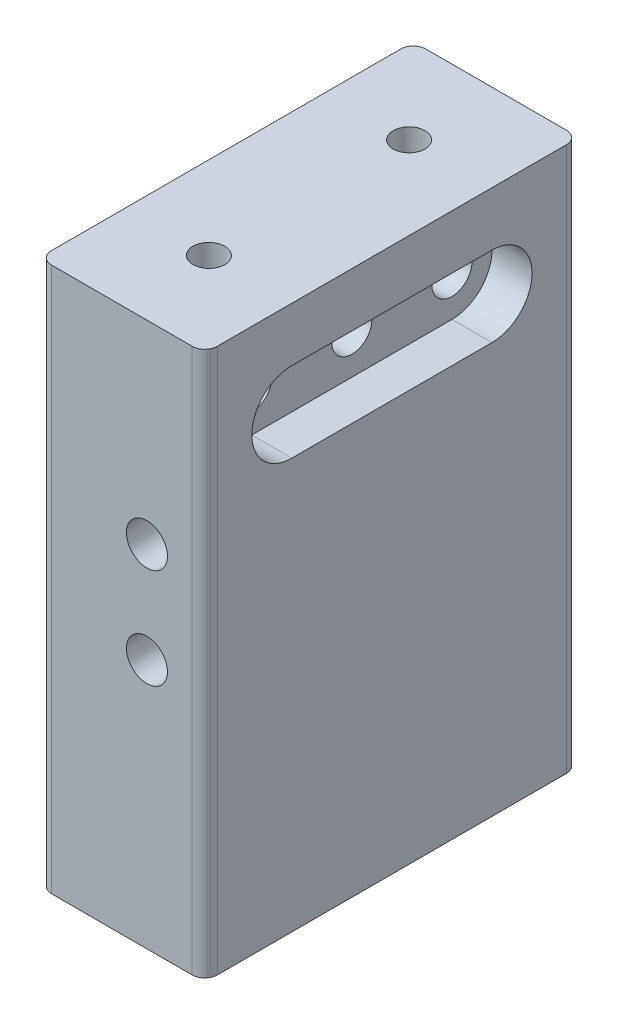
SolidWorks part; units mm, degrees
material "6061-T6 (SS)"
ref_plane "Front Plane" through (0, 0, 0) normal (0, 0, 1) x (1, 0, 0)
ref_plane "Top Plane" through (0, 0, 0) normal (0, 1, 0) x (1, 0, 0)
ref_plane "Right Plane" through (0, 0, 0) normal (1, 0, 0) x (0, 0, -1)
sketch "Sketch1" plane through (0, 0, 0) normal (0, 1, 0) x (1, 0, 0)
  line L1 (-10.5156, -23.7427) -> (10.5156, -23.7427)
  line L2 (-10.5156, -23.7427) -> (-10.5156, 23.7426)
  line L3 (-10.5156, 23.7426) -> (10.5156, 23.7426)
  line L4 (10.5156, -23.7427) -> (10.5156, 23.7426)
  line L5 (-10.5156, -23.7427) -> (10.5156, 23.7426) construction
  line L6 (-10.5156, 23.7426) -> (10.5156, -23.7427) construction
  point P0 (0, 0)
  dimension "D1" = 21.0312
  dimension "D2" = 47.4853
extrude "Boss-Extrude1" add sketch "Sketch1" along normal mid plane 63.5
sketch "Sketch2" plane through (0, 0, 23.7427) normal (0, 0, 1) x (1, 0, 0)
  line L5 (-10.5156, 31.75) -> (10.5156, 31.75) construction
  circle A1 centre (3.175, 0) radius 2.6035
  circle A2 centre (3.175, 12.7) radius 2.6035
  dimension "D3" = 19.05
  dimension "D1" = 7.3406
  dimension "D2" = 5.207
  dimension "D4" = 12.7
extrude "Cut-Extrude1" cut sketch "Sketch2" against normal through all
sketch "Sketch4" plane through (10.5156, 0, 0) normal (1, 0, 0) x (0, 0, -1)
  line L0 (-23.7427, 31.75) -> (23.7426, 31.75) construction
  circle A0 centre (-12.7, 25.4) radius 2.5527
  circle A1 centre (12.7, 25.4) radius 2.5527
  circle A2 centre (0, 25.4) radius 2.5527
  dimension "D5" = 5.1054
  dimension "D1" = 6.35
  dimension "D3" = 12.7
  dimension "D4" = 12.7
extrude "Cut-Extrude3" cut sketch "Sketch4" against normal through all
fillet "Fillet1" radius 1.5875 4 edges at (10.5156, 0, 23.7427) (-10.5156, 0, 23.7427) (-10.5156, 0, -23.7426) (10.5156, 0, -23.7426)
sketch "Sketch7" plane through (10.5156, 0, 0) normal (1, 0, 0) x (0, 0, -1)
  line L0 (-12.7, 25.4) -> (12.7, 25.4) construction
  line L1 (-12.7, 30.48) -> (12.7, 30.48)
  line L2 (-12.7, 20.32) -> (12.7, 20.32)
  arc A0 (-12.7, 30.48) -> (-12.7, 20.32) centre (-12.7, 25.4) ccw
  arc A1 (12.7, 20.32) -> (12.7, 30.48) centre (12.7, 25.4) ccw
  point P4 (0, 25.4)
  dimension "D1" = 5.08
extrude "Cut-Extrude5" cut sketch "Sketch7" against normal blind 5.08
sketch "Sketch8" plane through (0, 31.75, 0) normal (0, 1, 0) x (1, 0, 0)
  line L4 (-8.9281, -23.7427) -> (8.9281, -23.7427)
  line L5 (10.5156, -22.1552) -> (10.5156, 22.1551)
  line L6 (8.9281, 23.7426) -> (-8.9281, 23.7426)
  line L7 (-10.5156, 22.1551) -> (-10.5156, -22.1552)
  line L8 (-8.9281, -23.7427) -> (8.9281, -23.7427)
  line L9 (10.5156, -22.1552) -> (10.5156, 22.1551)
  line L10 (8.9281, 23.7426) -> (-8.9281, 23.7426)
  line L11 (-10.5156, 22.1551) -> (-10.5156, -22.1552)
  arc A4 (8.9281, -23.7427) -> (10.5156, -22.1552) centre (8.9281, -22.1552) ccw
  arc A5 (10.5156, 22.1551) -> (8.9281, 23.7426) centre (8.9281, 22.1551) ccw
  arc A6 (-8.9281, 23.7426) -> (-10.5156, 22.1551) centre (-8.9281, 22.1551) ccw
  arc A7 (-8.9281, 23.7426) -> (-10.5156, 22.1551) centre (-8.9281, 22.1551) ccw
  arc A8 (8.9281, -23.7427) -> (10.5156, -22.1552) centre (8.9281, -22.1552) ccw
  arc A9 (10.5156, 22.1551) -> (8.9281, 23.7426) centre (8.9281, 22.1551) ccw
  arc A10 (-10.5156, -22.1552) -> (-8.9281, -23.7427) centre (-8.9281, -22.1552) ccw
  arc A11 (-10.5156, -22.1552) -> (-8.9281, -23.7427) centre (-8.9281, -22.1552) ccw
  dimension "D1" = 0
extrude "Boss-Extrude2" add sketch "Sketch8" along normal blind 5.588
sketch "Sketch9" plane through (0, 37.338, 0) normal (0, 1, 0) x (1, 0, 0)
  line L0 (-10.5156, 0) -> (10.5156, 0) construction
  line L1 (-10.5156, 22.1551) -> (-10.5156, -22.1552) construction
  line L2 (10.5156, -22.1552) -> (10.5156, 22.1551) construction
  circle A0 centre (0, 12.7) radius 2.0193
  circle A2 centre (0, -12.7) radius 2.0193
  dimension "D2" = 4.0386
  dimension "D1" = 12.7
  dimension "D3" = 10.5156
extrude "Cut-Extrude6" cut sketch "Sketch9" against normal blind 5.08
